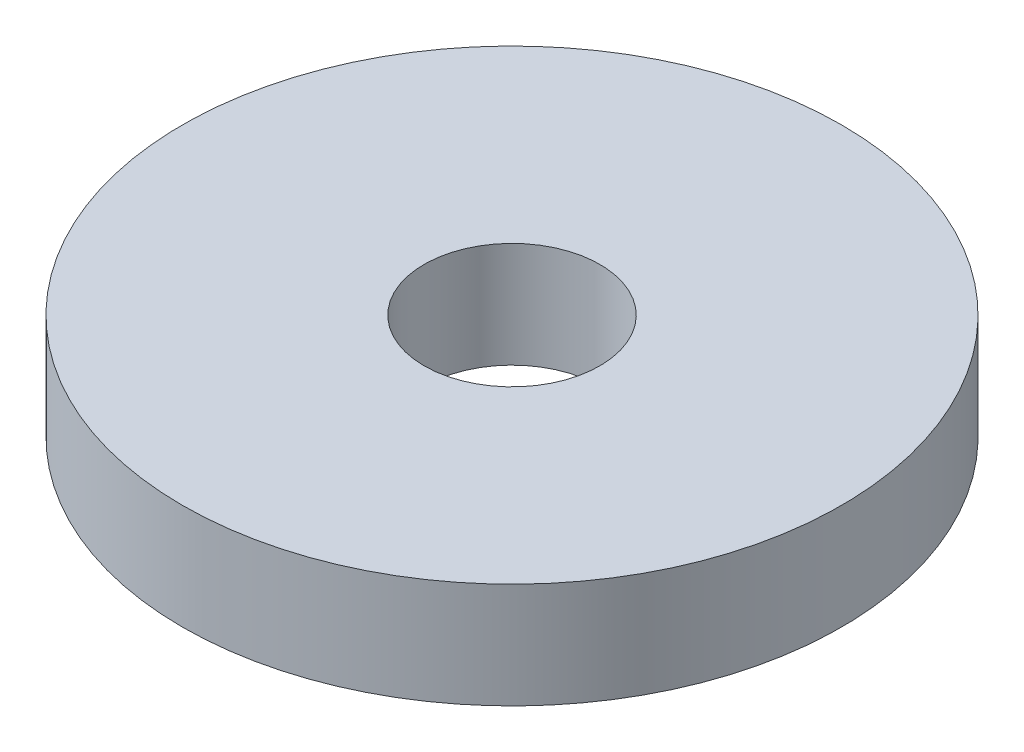
SolidWorks part; units mm, degrees
ref_plane "Front Plane" through (0, 0, 0) normal (0, 0, 1) x (1, 0, 0)
ref_plane "Top Plane" through (0, 0, 0) normal (0, 1, 0) x (1, 0, 0)
ref_plane "Right Plane" through (0, 0, 0) normal (1, 0, 0) x (0, 0, -1)
sketch "Sketch1" plane through (0, 0, 0) normal (0, 1, 0) x (1, 0, 0)
  circle A0 centre (0, 0) radius 37.5
  dimension "FLANGE_OD" = 75
extrude "Boss-Extrude1" add sketch "Sketch1" along normal blind 12
sketch "Sketch2" plane through (0, 0, 0) normal (0, 1, 0) x (1, 0, 0)
  circle A0 centre (0, 0) radius 10
  dimension "BORE_D" = 20
extrude "Cut-Extrude1" cut sketch "Sketch2" along normal through all
sketch "Sketch3" plane through (0, 12, 0) normal (0, 1, 0) x (1, 0, 0)
  circle A0 centre (0, 0) radius 7.2822 construction
  circle A1 centre (-7.2822, 0) radius 1.5166
  dimension "BOLT_D" = 3.0332
  dimension "BOLT_PCD" = 14.5644
extrude "Cut-Extrude2" cut sketch "Sketch3" against normal blind 9.0824 rebuild error yes
pattern_circular "CirPattern1" count 6 over 360 rebuild error yes
